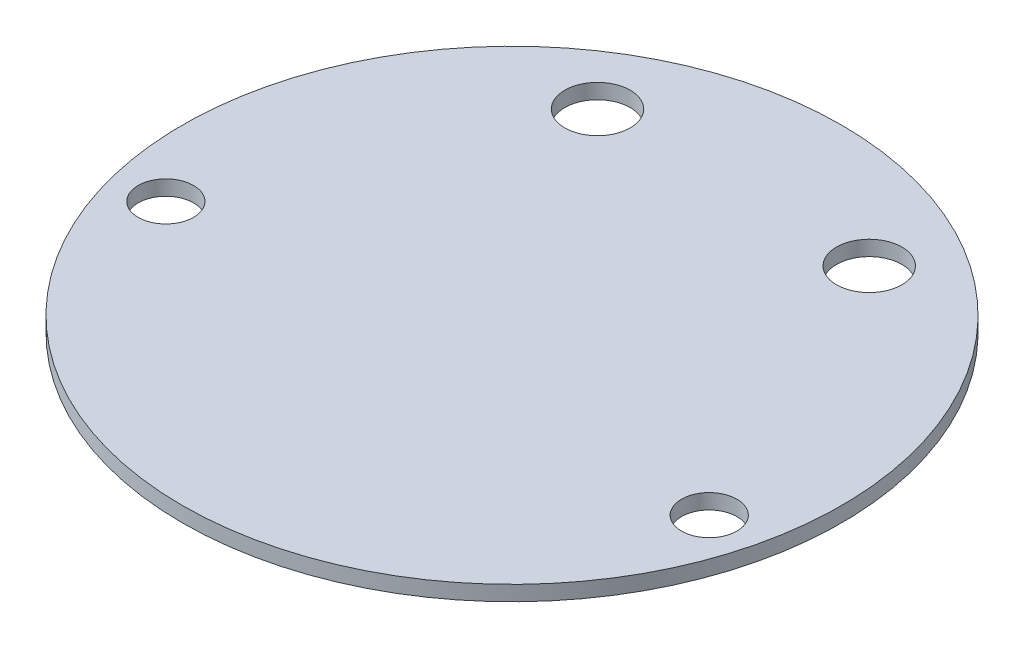
SolidWorks part; units mm, degrees
material "ABS"
ref_plane "Front Plane" through (0, 0, 0) normal (0, 0, 1) x (1, 0, 0)
ref_plane "Top Plane" through (0, 0, 0) normal (0, 1, 0) x (1, 0, 0)
ref_plane "Right Plane" through (0, 0, 0) normal (1, 0, 0) x (0, 0, -1)
sketch "Sketch1" plane through (0, 0, 0) normal (0, 1, 0) x (1, 0, 0)
  line L0 (-27, -7.4) -> (27, -7.4) construction
  line L1 (-13.5, 22) -> (13.5, 22) construction
  circle A0 centre (0, 0) radius 32.75
  circle A1 centre (-27, -7.4) radius 2.75
  circle A2 centre (27, -7.4) radius 2.75
  circle A3 centre (-13.5, 22) radius 3.25
  circle A4 centre (13.5, 22) radius 3.25
  point P7 (0, -7.4)
  point P12 (0, 22)
  dimension "D2" = 5.5
  dimension "D3" = 65.5
  dimension "D5" = 6.5
  dimension "D1" = 54
  dimension "D4" = 7.4
  dimension "D6" = 22
  dimension "D7" = 27
extrude "Boss-Extrude1" add sketch "Sketch1" along normal blind 1.5
